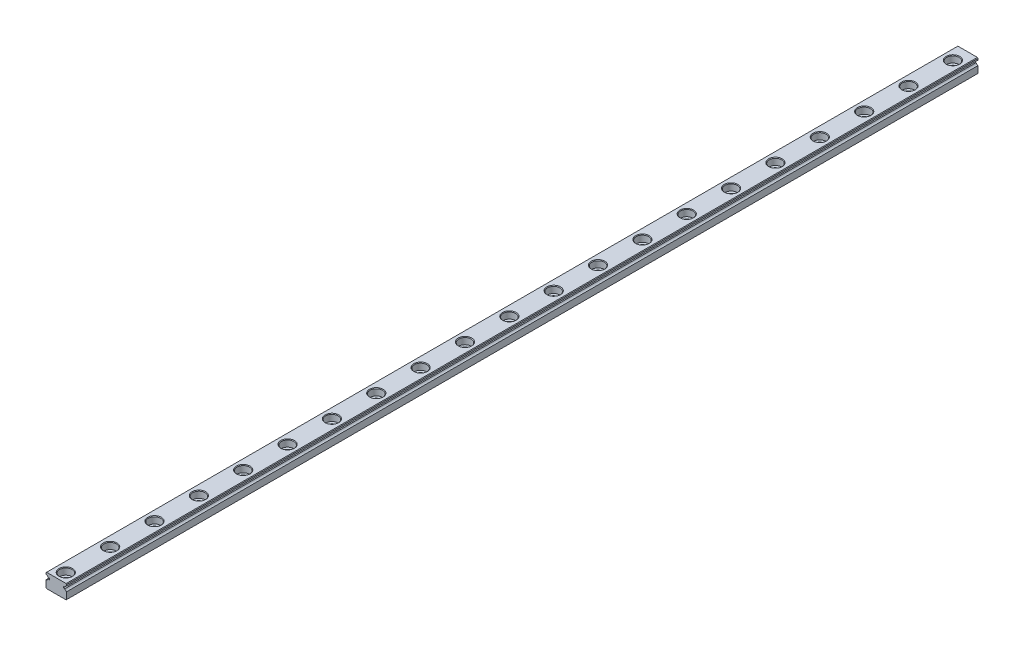
SolidWorks part; units mm, degrees
material "AISI 1020"
ref_plane "Спереди" through (0, 0, 0) normal (0, 0, 1) x (1, 0, 0)
ref_plane "Сверху" through (0, 0, 0) normal (0, 1, 0) x (1, 0, 0)
ref_plane "Справа" through (0, 0, 0) normal (1, 0, 0) x (0, 0, -1)
sketch "Sketch1" plane through (0, 0, 0) normal (0, 0, 1) x (1, 0, 0)
  line L0 (0, 0) -> (0, 4.3706) construction
  line L1 (-3.3, -2.4) -> (3.3, -2.4)
  line L2 (-3.5, -2.2) -> (-3.5, 0.1063)
  line L3 (-3.3, 2.4) -> (3.3, 2.4)
  line L4 (3.5, -2.2) -> (3.5, 0.1063)
  line L5 (-3.5, -2.4) -> (3.5, 2.4) construction
  line L6 (-3.5, 2.4) -> (3.5, -2.4) construction
  line L7 (-3.5, 1.6937) -> (-3.5, 2.2)
  line L8 (3.5, 1.6937) -> (3.5, 2.2)
  line L9 (-3.5, -2.2) -> (-3.3, -2.4)
  line L10 (3.3, -2.4) -> (3.5, -2.2)
  line L11 (3.3, 2.4) -> (3.5, 2.2)
  line L12 (-3.5, 2.2) -> (-3.3, 2.4)
  line L13 (2.8401, 0.65) -> (2.3401, 0.65)
  line L14 (-2.8401, 0.65) -> (-2.3401, 0.65)
  line L15 (2.3401, 0.65) -> (2.3401, 1.15)
  line L16 (-2.8401, 1.15) -> (-2.3401, 1.15)
  line L17 (-2.3401, 0.65) -> (-2.3401, 1.15)
  line L18 (2.8401, 1.15) -> (2.3401, 1.15)
  arc A0 (-3.5, 1.6937) -> (-2.8401, 1.15) centre (-3.6, 0.9) cw
  arc A1 (3.5, 1.6937) -> (2.8401, 1.15) centre (3.6, 0.9) ccw
  arc A2 (-2.8401, 0.65) -> (-3.5, 0.1063) centre (-3.6, 0.9) cw
  arc A3 (2.8401, 0.65) -> (3.5, 0.1063) centre (3.6, 0.9) ccw
  point P0 (0, 0)
  dimension "D4" = 0.8
  dimension "D5" = 0.1
  dimension "D1" = 7
  dimension "D2" = 4.8
  dimension "D3" = 1.5
  dimension "D6" = 0.5
  dimension "D7" = 0.5
extrude "Extrude1" add sketch "Sketch1" along normal offset from surface (308.2 mm away) 1
sketch "Sketch2" plane through (0, 2.4, 0) normal (0, 1, 0) x (1, 0, 0)
  line L0 (0, 0) -> (0, -5) construction
  circle A0 centre (0, -5) radius 1.2
  circle A1 centre (0, -5) radius 2.1
  dimension "D1" = 2.4
  dimension "D2" = 4.2
  dimension "D3" = 5
extrude "Extrude2" cut sketch "Sketch2" against normal up to next contours A0 region at (0, 2.4, 5)
extrude "Extrude4" cut sketch "Sketch" against normal blind 2.3
sketch "Sketch" plane through (0, 2.4, 0) normal (0, 1, 0) x (1, 0, 0) same geometry as "Sketch2"
chamfer "Chamfer1" distance 0.2 angle 45 2 edges at (0, -2.4, 6.2) (0, 2.4, 7.1)
pattern_linear "LPattern1" count 21 spacing 15 along (0, 0, 1) of "Extrude4", "Chamfer1", "Extrude2"
